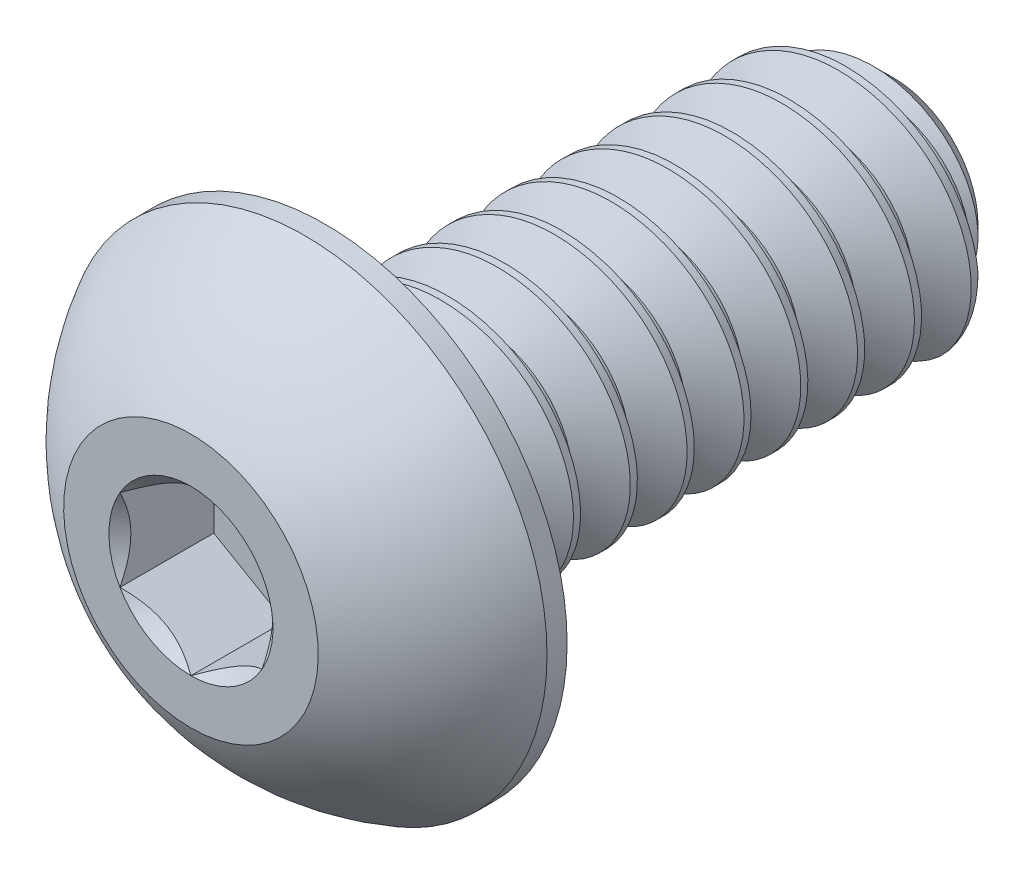
SolidWorks part; units mm, degrees
ref_plane "Front" through (0, 0, 0) normal (0, 0, 1) x (1, 0, 0)
ref_plane "Top" through (0, 0, 0) normal (0, 1, 0) x (1, 0, 0)
ref_plane "Right" through (0, 0, 0) normal (1, 0, 0) x (0, 0, -1)
sketch "Sketch1" plane through (0, 0, 0) normal (1, 0, 0) x (0, 0, -1)
  line L2 (1.4986, 1.4224) -> (7.8486, 1.4224)
  line L3 (7.8486, 1.4224) -> (7.8486, 0)
  line L4 (7.8486, 0) -> (1.4986, 0)
  line L6 (1.2738, 2.7051) -> (1.4986, 2.7051) construction
  line L7 (7.8486, 1.4224) -> (7.8486, -1.4224) construction
  line L8 (0, 0) -> (1.4986, 0) construction
  line L9 (1.4986, 2.7051) -> (1.4986, -2.7051) construction
  line L11 (1.4986, 1.4224) -> (1.4986, 0)
  line L13 (0, 0.7937) -> (0, -0.7937) construction
  line L14 (0, 0.7937) -> (0, 1.4224) construction
  arc A3 (0, 1.4224) -> (1.2738, 2.7051) centre (2.7151, 0) cw construction
  dimension "D1" = 0.2248
revolve "Revolve1" add sketch "Sketch1" angle 360 mid plane about L4
sketch "Sketch3" plane through (0, 0, -7.8486) normal (0, 0, -1) x (-1, 0, 0)
  circle A0 centre (0, 0) radius 1.4224
curve "Helix/Spiral1" pitch 0.635 height 7.8486 radius 1.4224 centre (0, 0, -7.8486) axis (0, 0, 1) start towards (0, 1, 0)
sketch "Sketch2" plane through (0, 0, 0) normal (1, 0, 0) x (0, 0, -1)
  line L0 (7.8486, 1.4224) -> (8.4042, 1.4224)
  line L1 (8.4042, 1.4224) -> (8.1661, 1.01)
  line L2 (8.1661, 1.01) -> (8.0867, 1.01)
  line L3 (8.0867, 1.01) -> (7.8486, 1.4224)
  line L4 (7.9677, 1.2162) -> (8.2852, 1.2162) construction
  dimension "D1" = 60
  dimension "D2" = 0.0794
  dimension "D3" = 0.3175
chamfer "Chamfer1" distance 0.4763 angle 45 1 edges at (0, 1.4224, -7.8486)
sweep "Cut-Sweep1" cut profiles "Sketch2" path "Helix/Spiral1"
sketch "Sketch7" plane through (0, 0, 0) normal (1, 0, 0) x (0, 0, -1)
  line L6 (1.2738, 2.7051) -> (1.4986, 2.7051) construction
  line L8 (0, 0) -> (1.4986, 0) construction
  line L11 (1.4986, 2.7051) -> (1.4986, -2.7051) construction
  line L12 (1.2738, 2.7051) -> (1.4986, 2.7051)
  line L13 (0, 0) -> (1.4986, 0)
  line L14 (0, 0.7937) -> (0, -0.7937) construction
  line L15 (1.4986, 2.7051) -> (1.4986, 0)
  line L16 (0, 1.4224) -> (0, 0)
  arc A2 (1.2738, 2.7051) -> (0, 1.4224) centre (2.7151, 0) ccw construction
  arc A3 (1.2738, 2.7051) -> (0, 1.4224) centre (2.7151, 0) ccw
revolve "Revolve2" add sketch "Sketch7" angle 360 mid plane about L13
sketch "Sketch5" plane through (0, 0, 0) normal (0, 0, 1) x (1, 0, 0)
  line L1 (0.7937, -0.4583) -> (0.7937, 0.4583)
  line L2 (0.7937, 0.4583) -> (0, 0.9165)
  line L3 (0, 0.9165) -> (-0.7938, 0.4583)
  line L4 (-0.7938, 0.4583) -> (-0.7937, -0.4583)
  line L5 (-0.7937, -0.4583) -> (0, -0.9165)
  line L6 (0, -0.9165) -> (0.7937, -0.4583)
  circle A0 centre (0, 0) radius 0.7937 construction
extrude "Cut-Extrude2" cut sketch "Sketch5" against normal blind 1.049
sketch "Sketch6" plane through (0, 0, 0) normal (0, 0, 1) x (1, 0, 0)
  circle A0 centre (0, 0) radius 0.9165
extrude "Cut-Extrude3" cut sketch "Sketch6" against normal blind 1.049 draft 45
sketch "Sketch9" [suppressed] plane through (0, 0, -1.4986) normal (0, 0, 1) x (1, 0, 0)
  circle A2 centre (0, 0) radius 1.4224
extrude "Boss-Extrude2" [suppressed] add sketch "Sketch9" against normal offset from surface (6.35 mm away) 22.225 up to face at (0, 0.9462, -7.8486)
sketch "Sketch10" plane through (0, 0, 0) normal (1, 0, 0) x (0, 0, -1)
  line L0 (7.8486, 1.4224) -> (7.8486, -1.4224) construction
  point P0 (6.8961, -1.4224)
  dimension "D1" = 0.9525
equation "\"D3@Helix/Spiral1\" = \"Lg@Sketch1\" + \"Head Ht@Sketch1\""
equation "\"D2@Sketch2\" = \"D4@Helix/Spiral1\" * .125"
equation "\"D3@Sketch2\" = \"D4@Helix/Spiral1\" * .5"
equation "\"D1@Chamfer1\" = \"D4@Helix/Spiral1\" * .75"
equation "\"D1@Cut-Extrude2\" = \"Head Ht@Sketch1\" * .7"
equation "\"D1@Sketch1\" = \"Head Ht@Sketch1\" * .15"
equation "\"D1@Sketch10\" = \"D4@Helix/Spiral1\" * 1.5"
equation "\"D1@Cut-Extrude3\" = \"D1@Cut-Extrude2\""
